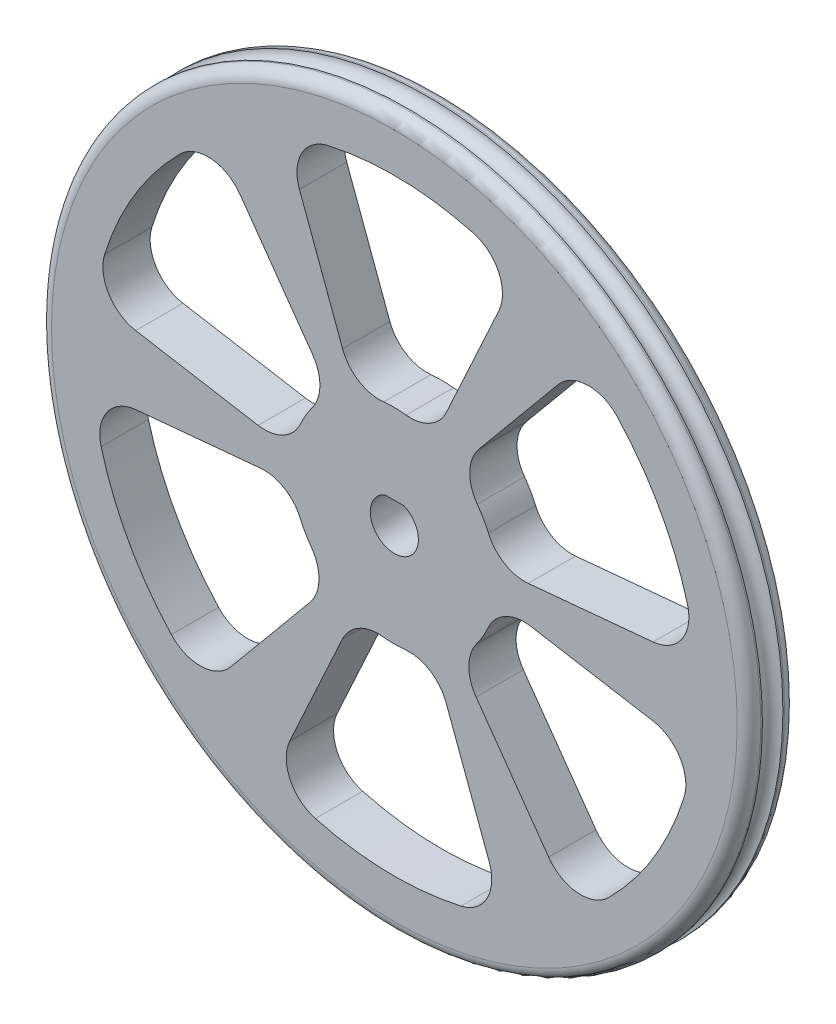
SolidWorks part; units mm, degrees
ref_plane "Plan de face" through (0, 0, 0) normal (0, 0, 1) x (1, 0, 0)
ref_plane "Plan de dessus" through (0, 0, 0) normal (0, 1, 0) x (1, 0, 0)
ref_plane "Plan de droite" through (0, 0, 0) normal (1, 0, 0) x (0, 0, -1)
sketch "Esquisse2" plane through (0, 0, 0) normal (1, 0, 0) x (0, 0, -1)
  line L0 (0, 128.7879) -> (0, -38.5432) construction
  line L1 (-77.2545, 0) -> (83.8756, 0) construction
  line L2 (3, 0) -> (-3, 0)
  line L4 (-3, 0) -> (-3, 43.5)
  line L5 (-1.5, 45) -> (-1.3, 45)
  line L6 (-1.3, 45) -> (-1.3, 48.0051) construction
  line L7 (-1.3, 48.0051) -> (0, 48.0051) construction
  line L8 (-1.3, 45) -> (1.3, 45) construction
  line L9 (1.3, 48.0051) -> (0, 48.0051) construction
  line L10 (1.3, 45) -> (1.3, 48.0051) construction
  line L11 (3, 0) -> (3, 43.5)
  line L12 (-3, 45) -> (3, 45) construction
  line L13 (77.2545, 0) -> (-83.8756, 0) construction
  line L15 (1.3, 45) -> (1.5, 45)
  arc A1 (-1.3, 45) -> (1.3, 45) centre (0, 45) ccw
  arc A2 (3, 43.5) -> (1.5, 45) centre (1.5, 43.5) ccw
  arc A3 (-3, 43.5) -> (-1.5, 45) centre (-1.5, 43.5) cw
  point P23 (0, 0)
  dimension "D2" = 1.5
  dimension "D1" = 45
  dimension "D3" = 1.3
  dimension "D6" = 3
revolve "Révolution1" add sketch "Esquisse2" angle 360 about L1
sketch "Esquisse3" plane through (0, 0, 0) normal (0, 0, 1) x (1, 0, 0)
  line L0 (0, 0) -> (22.2154, 0) construction
  line L1 (0, 0) -> (0, 9.136) construction
  line L2 (-1.2093, 2.8) -> (1.2093, 2.8)
  line L3 (-13.5007, -3.05) -> (10.4711, -3.05) construction
  arc A0 (-1.2093, 2.8) -> (1.2093, 2.8) centre (0, 0) ccw
  point P8 (0, 2.8)
  dimension "D1" = 3.05
  dimension "D2" = 2.8
  dimension "D3" = 5.85
extrude "Enlèv. mat.-Extru.3" cut sketch "Esquisse3" against normal through all both and the other way through all contours L2 A0
sketch "Esquisse4" plane through (0, 0, 0) normal (1, 0, 0) x (0, 0, -1)
  line L0 (0, 0) -> (46.0868, 0) construction
  arc A0 (-1.3, 45) -> (1.3, 45) centre (0, 45) ccw construction
  arc A1 (-1.3, 45) -> (1.3, 45) centre (0, 45) ccw
  circle A2 centre (0, 45) radius 1.3
  dimension "D2" = 2.6
  dimension "D1" = 45
revolve "Révolution2" [suppressed] add sketch "Esquisse4" angle 360 about L0
sketch "Esquisse5" plane through (0, 0, 3) normal (0, 0, 1) x (1, 0, 0)
  line L0 (-12.0456, 30.9445) -> (-6.5674, 16.164)
  line L1 (63.8365, 28.9354) -> (63.8365, 29.0818)
  line L2 (6.6185, 15.7936) -> (13.2609, 30.2596)
  line L3 (16.9869, 2.1651) -> (32.836, 3.6455)
  line L4 (20.7759, 25.904) -> (10.7147, 13.7695)
  line L5 (10.3684, -13.6286) -> (19.5751, -26.614)
  line L6 (32.8215, -5.0405) -> (17.2821, -2.3945)
  line L7 (-6.6185, -15.7936) -> (-13.2609, -30.2596)
  line L8 (12.0456, -30.9445) -> (6.5674, -16.164)
  line L9 (-16.9869, -2.1651) -> (-32.836, -3.6455)
  line L10 (-20.7759, -25.904) -> (-10.7147, -13.7695)
  line L11 (-10.3684, 13.6286) -> (-19.5751, 26.614)
  line L12 (-32.8215, 5.0405) -> (-17.2821, 2.3945)
  arc A0 (1.4983, 12.9134) -> (-1.3571, 12.929) centre (0, 0) ccw
  arc A1 (10.018, 37.1738) -> (-8.4553, 37.5601) centre (0, 0) ccw
  circle A2 centre (0, 0) radius 43.5 construction
  arc A3 (10.018, 37.1738) -> (13.2609, 30.2596) centre (8.717, 32.346) cw
  arc A4 (1.4983, 12.9134) -> (6.6185, 15.7936) centre (2.0746, 17.88) ccw
  arc A5 (-12.0456, 30.9445) -> (-8.4553, 37.5601) centre (-7.3572, 32.6821) cw
  arc A6 (-6.5674, 16.164) -> (-1.3571, 12.929) centre (-1.879, 17.9017) ccw
  arc A7 (11.9325, 5.1591) -> (16.9869, 2.1651) centre (16.5219, 7.1434) ccw
  arc A8 (37.2024, 9.911) -> (32.836, 3.6455) centre (32.371, 8.6239) cw
  arc A9 (37.2024, 9.911) -> (28.3003, 26.1025) centre (0, 0) ccw
  arc A10 (20.7759, 25.904) -> (28.3003, 26.1025) centre (24.6249, 22.7126) cw
  arc A11 (10.7147, 13.7695) -> (10.5183, 7.6398) centre (14.5638, 10.5781) ccw
  arc A12 (11.9325, 5.1591) -> (10.5183, 7.6398) centre (0, 0) ccw
  arc A13 (10.4342, -7.7543) -> (10.3684, -13.6286) centre (14.4473, -10.7367) ccw
  arc A14 (27.1844, -27.2628) -> (19.5751, -26.614) centre (23.654, -23.7221) cw
  arc A15 (27.1844, -27.2628) -> (36.7556, -11.4575) centre (0, 0) ccw
  arc A16 (32.8215, -5.0405) -> (36.7556, -11.4575) centre (31.9822, -9.9695) cw
  arc A17 (17.2821, -2.3945) -> (11.8754, -5.2892) centre (16.4428, -7.3235) ccw
  arc A18 (10.4342, -7.7543) -> (11.8754, -5.2892) centre (0, 0) ccw
  arc A19 (-1.4983, -12.9134) -> (-6.6185, -15.7936) centre (-2.0746, -17.88) ccw
  arc A20 (-10.018, -37.1738) -> (-13.2609, -30.2596) centre (-8.717, -32.346) cw
  arc A21 (-10.018, -37.1738) -> (8.4553, -37.5601) centre (0, 0) ccw
  arc A22 (12.0456, -30.9445) -> (8.4553, -37.5601) centre (7.3572, -32.6821) cw
  arc A23 (6.5674, -16.164) -> (1.3571, -12.929) centre (1.879, -17.9017) ccw
  arc A24 (-1.4983, -12.9134) -> (1.3571, -12.929) centre (0, 0) ccw
  arc A25 (-11.9325, -5.1591) -> (-16.9869, -2.1651) centre (-16.5219, -7.1434) ccw
  arc A26 (-37.2024, -9.911) -> (-32.836, -3.6455) centre (-32.371, -8.6239) cw
  arc A27 (-37.2024, -9.911) -> (-28.3003, -26.1025) centre (0, 0) ccw
  arc A28 (-20.7759, -25.904) -> (-28.3003, -26.1025) centre (-24.6249, -22.7126) cw
  arc A29 (-10.7147, -13.7695) -> (-10.5183, -7.6398) centre (-14.5638, -10.5781) ccw
  arc A30 (-11.9325, -5.1591) -> (-10.5183, -7.6398) centre (0, 0) ccw
  arc A31 (-10.4342, 7.7543) -> (-10.3684, 13.6286) centre (-14.4473, 10.7367) ccw
  arc A32 (-27.1844, 27.2628) -> (-19.5751, 26.614) centre (-23.654, 23.7221) cw
  arc A33 (-27.1844, 27.2628) -> (-36.7556, 11.4575) centre (0, 0) ccw
  arc A34 (-32.8215, 5.0405) -> (-36.7556, 11.4575) centre (-31.9822, 9.9695) cw
  arc A35 (-17.2821, 2.3945) -> (-11.8754, 5.2892) centre (-16.4428, 7.3235) ccw
  arc A36 (-10.4342, 7.7543) -> (-11.8754, 5.2892) centre (0, 0) ccw
  point P12 (15.5405, 35.2242)
  point P15 (4.8961, 12.0427)
  point P18 (-13.8855, 35.9088)
  point P21 (-5.0208, 11.9913)
  point P85 (0, 0)
  dimension "D1" = 6
  dimension "D4" = 5
  dimension "D5" = 5
  dimension "D2" = 13
  dimension "D3" = 45
extrude "Enlèv. mat.-Extru.8" cut sketch "Esquisse5" against normal through all both contours A36 A31 L11 A32 A33 A34 L12 A35 | A30 A25 L9 A26 A27 A28 L10 A29 | A24 A19 L7 A20 A21 A22 L8 A23 | A18 A13 L5 A14 A15 A16 L6 A17 | A12 A7 L3 A8 A9 A10 L4 A11 | L0 A6 A0 A4 L2 A3 A1 A5 region at (0.4727, 27.122, 3) region at (23.7247, 13.1517, 3) region at (23.252, -13.9703, 3) region at (-0.4727, -27.122, 3) region at (-23.7247, -13.1517, 3) region at (-23.252, 13.9703, 3)
